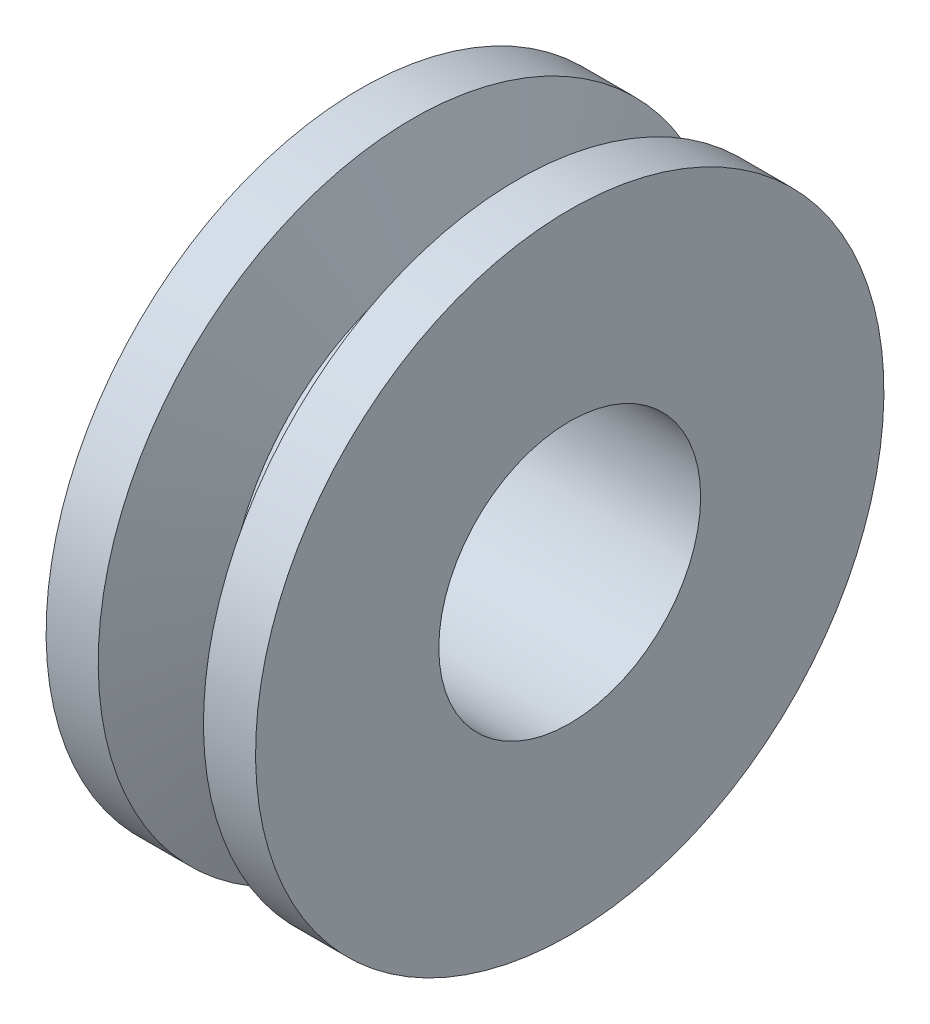
SolidWorks part; units mm, degrees
material "6061-T6 (SS)"
ref_plane "Front Plane" through (0, 0, 0) normal (0, 0, 1) x (1, 0, 0)
ref_plane "Top Plane" through (0, 0, 0) normal (0, 1, 0) x (1, 0, 0)
ref_plane "Right Plane" through (0, 0, 0) normal (1, 0, 0) x (0, 0, -1)
sketch "Sketch1" plane through (0, 0, 0) normal (0, 0, 1) x (1, 0, 0)
  line L0 (-10, 0) -> (10, 0)
  line L1 (10, 0) -> (10, 30)
  line L2 (10, 30) -> (5.0257, 30)
  line L3 (5.0257, 30) -> (1.75, 21)
  line L4 (1.75, 21) -> (-1.75, 21)
  line L5 (-1.75, 21) -> (-5.0257, 30)
  line L6 (-5.0257, 30) -> (-10, 30)
  line L7 (-10, 30) -> (-10, 0)
  line L8 (10, 6) -> (-10, 6)
  line L9 (10, 12.5) -> (12.5, 12.5)
  line L10 (12.5, 12.5) -> (12.5, 6)
  line L11 (12.5, 6) -> (10, 6)
  line L12 (-10, 12.5) -> (-15, 12.5)
  line L13 (-15, 12.5) -> (-15, 6)
  line L14 (-15, 6) -> (-10, 6)
  line L15 (-5, 29.9293) -> (5, 29.9293) construction
  line L16 (-4.25, 27.8687) -> (4.25, 27.8687) construction
  line L17 (-2.0882, 21.9293) -> (2.0882, 21.9293) construction
  point P8 (0, 0)
  dimension "D1" = 30
  dimension "D2" = 40
  dimension "D3" = 9
  dimension "D4" = 10.0515
  dimension "D5" = 20
  dimension "D6" = 6
  dimension "D7" = 2.5
  dimension "D8" = 12.5
  dimension "D9" = 5
  dimension "D10" = 3.5
  dimension "D11" = 8
  dimension "D12" = 10
  dimension "D13" = 8.5
  dimension "D14" = 27.8687
revolve "Revolve1" add sketch "Sketch1" angle 360 about L0 region at (0, 3, 0) region at (0, 16.803, 0)
sketch "Sketch2" plane through (10, 0, 0) normal (1, 0, 0) x (0, 0, -1)
  line L1 (-2, 14.5) -> (2, 14.5)
  line L2 (-2, 14.5) -> (-2, 10.5)
  line L3 (-2, 10.5) -> (2, 10.5)
  line L4 (2, 14.5) -> (2, 10.5)
  line L5 (-2, 14.5) -> (2, 10.5) construction
  line L6 (-2, 10.5) -> (2, 14.5) construction
  circle A3 centre (18, 0) radius 3
  circle A4 centre (9, -15.5885) radius 3
  circle A5 centre (-9, -15.5885) radius 3
  circle A6 centre (-18, 0) radius 3
  circle A7 centre (-9, 15.5885) radius 3
  circle A8 centre (9, 15.5885) radius 3
  circle A9 centre (0, 0) radius 12.5
  point P0 (0, 12.5)
  point P6 (0, 0)
  point P8 (-9, 17.3984)
  point P10 (0, 0)
  point P13 (0, 12.5)
  point P26 (0, 0)
  dimension "D2" = 6
  dimension "D5" = 25
  dimension "D1" = 4
  dimension "D3" = 18
  dimension "D4" = 6
extrude "Cut-Extrude4" cut sketch "Sketch2" against normal blind 31 contours A9
